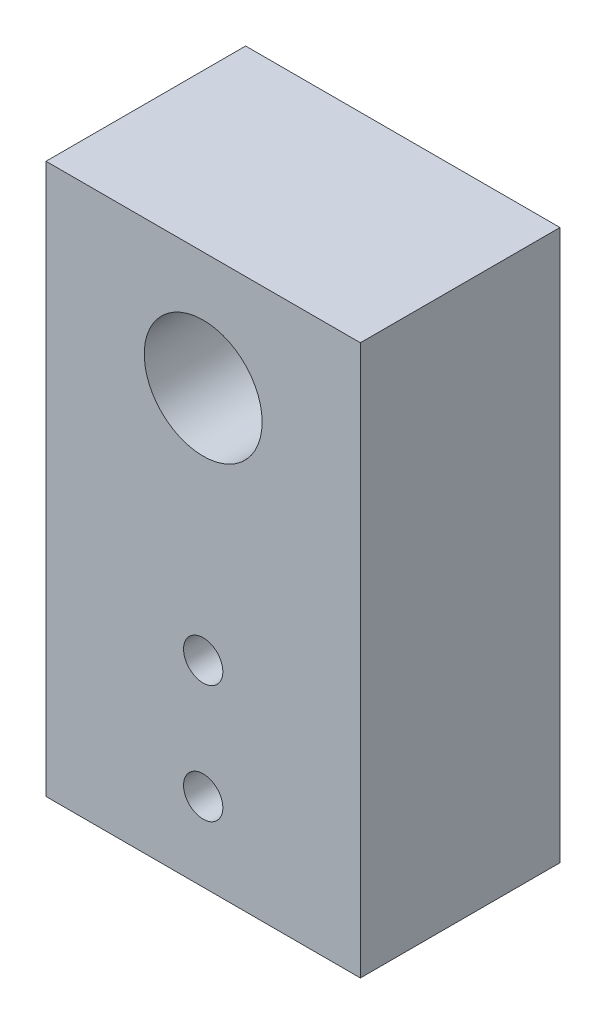
SolidWorks part; units mm, degrees
ref_plane "Front Plane" through (0, 0, 0) normal (0, 0, 1) x (1, 0, 0)
ref_plane "Top Plane" through (0, 0, 0) normal (0, 1, 0) x (1, 0, 0)
ref_plane "Right Plane" through (0, 0, 0) normal (1, 0, 0) x (0, 0, -1)
sketch "Sketch1" plane through (0, 0, 0) normal (0, 0, 1) x (1, 0, 0)
  line L0 (0, 35) -> (0, -35) construction
  line L1 (-20, -35) -> (20, -35)
  line L2 (-20, -35) -> (-20, 35)
  line L3 (-20, 35) -> (20, 35)
  line L4 (20, -35) -> (20, 35)
  line L5 (-20, -35) -> (20, 35) construction
  line L6 (-20, 35) -> (20, -35) construction
  circle A0 centre (0, 20) radius 7.5
  circle A1 centre (0, -10) radius 2.5
  circle A2 centre (0, -25) radius 2.5
  point P4 (0, 0)
  point P14 (0, 0)
  point P15 (0, 0)
  point P16 (0, 0)
  point P17 (0, 0)
  dimension "D3" = 15
  dimension "D4" = 5
  dimension "D5" = 5
  dimension "D1" = 40
  dimension "D2" = 70
  dimension "D6" = 10
  dimension "D7" = 15
  dimension "D8" = 55
extrude "Boss-Extrude1" add sketch "Sketch1" along normal blind 25.4
